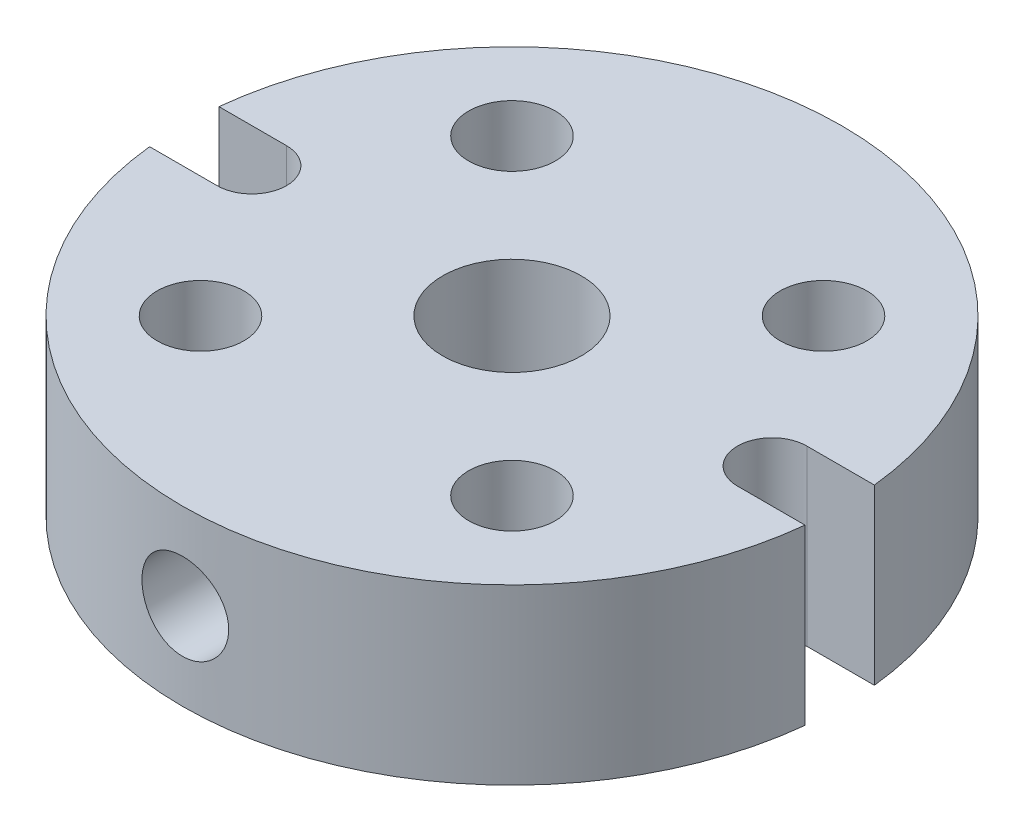
SolidWorks part; units mm, degrees
ref_plane "Front Plane" through (0, 0, 0) normal (0, 0, 1) x (1, 0, 0)
ref_plane "Top Plane" through (0, 0, 0) normal (0, 1, 0) x (1, 0, 0)
ref_plane "Right Plane" through (0, 0, 0) normal (1, 0, 0) x (0, 0, -1)
sketch "Sketch1" plane through (0, 0, 0) normal (0, 1, 0) x (1, 0, 0)
  line L0 (-9.5, 0) -> (9.5, 0) construction
  line L1 (0, 9.5) -> (0, -9.5) construction
  line L2 (0, 0) -> (6.7175, 6.7175) construction
  circle A0 centre (0, 0) radius 9.5
  circle A1 centre (0, 0) radius 2
  circle A2 centre (4.4901, 4.4901) radius 1.25
  circle A3 centre (-4.4901, 4.4901) radius 1.25
  circle A4 centre (4.4901, -4.4901) radius 1.25
  circle A5 centre (-4.4901, -4.4901) radius 1.25
  dimension "D1" = 19
  dimension "D2" = 4
  dimension "D3" = 2.5
  dimension "D4" = 6.35
  dimension "D5" = 45
extrude "Base shape" add sketch "Sketch1" along normal blind 5
ref_plane "Plane2" through (0, 0, 9.5) normal (0, 0, 1) x (1, 0, 0)
sketch "Sketch3" plane through (0, 0, 9.5) normal (0, 0, 1) x (1, 0, 0)
  line L0 (-9.5, 2.5) -> (9.5, 2.5) construction
  line L1 (-9.5, 5) -> (-9.5, 0) construction
  line L2 (9.5, 0) -> (9.5, 5) construction
  circle A0 centre (0, 2.5) radius 1.25
  dimension "D1" = 2.5
extrude "Grub screw cut" cut sketch "Sketch3" against normal up to next
sketch "Sketch4" plane through (0, 5, 0) normal (0, 1, 0) x (1, 0, 0)
  line L0 (-9.5, 0) -> (9.5, 0) construction
  line L1 (-9.4472, 0) -> (-7.5, 0) construction
  line L2 (-9.4472, 1) -> (-7.5, 1)
  line L3 (-9.4472, -1) -> (-7.5, -1)
  line L4 (0, 9.5) -> (0, -9.5) construction
  line L5 (9.4472, 0) -> (7.5, 0) construction
  line L6 (9.4472, 1) -> (7.5, 1)
  line L7 (9.4472, -1) -> (7.5, -1)
  circle A0 centre (0, 0) radius 9.5 construction
  arc A1 (-9.4472, 1) -> (-9.4472, -1) centre (-9.4472, 0) ccw
  arc A2 (-7.5, -1) -> (-7.5, 1) centre (-7.5, 0) ccw
  arc A3 (9.4472, 1) -> (9.4472, -1) centre (9.4472, 0) cw
  arc A4 (7.5, -1) -> (7.5, 1) centre (7.5, 0) cw
  point P7 (-8.4736, 0)
  point P18 (8.4736, 0)
  dimension "D1" = 15
  dimension "D2" = 2
extrude "Motor screw slots" cut sketch "Sketch4" against normal up to next
